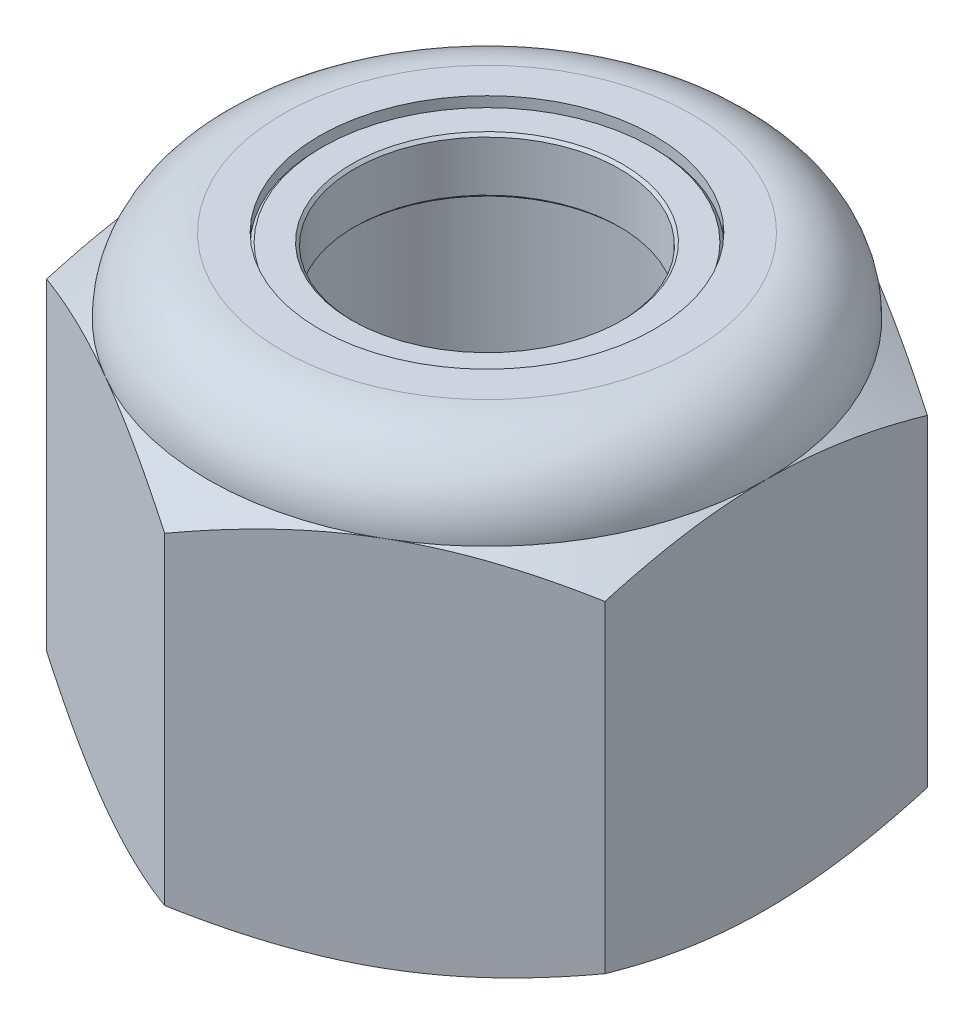
SolidWorks part; units mm, degrees
ref_plane "Front" through (0, 0, 0) normal (0, 0, 1) x (1, 0, 0)
ref_plane "Top" through (0, 0, 0) normal (0, 1, 0) x (1, 0, 0)
ref_plane "Right" through (0, 0, 0) normal (1, 0, 0) x (0, 0, -1)
sketch "Sketch1" plane through (0, 0, 0) normal (0, 1, 0) x (1, 0, 0)
  line L1 (0, 5.7735) -> (-5, 2.8868)
  line L2 (-5, 2.8868) -> (-5, -2.8868)
  line L3 (-5, -2.8868) -> (0, -5.7735)
  line L4 (0, -5.7735) -> (5, -2.8868)
  line L5 (5, -2.8868) -> (5, 2.8868)
  line L6 (5, 2.8868) -> (0, 5.7735)
  circle A0 centre (0, 0) radius 5 construction
  circle A1 centre (0, 0) radius 3
  dimension "Thread Dia" = 6
  dimension "Hex Flats" = 10
extrude "Extrude1" add sketch "Sketch1" along normal blind 8
sketch "Sketch2" plane through (0, 0, 0) normal (1, 0, 0) x (0, 0, -1)
  line L0 (5.7735, 8) -> (5.7735, 0) construction
  line L1 (5.7735, 8) -> (5.7735, 6.2201)
  line L2 (5.7735, 0.4466) -> (5, 0)
  line L3 (5, 0) -> (5.7735, 0)
  line L4 (5, 0) -> (-5, 0) construction
  line L5 (5.7735, 6.2201) -> (5, 6.6667)
  line L6 (2.8868, 8) -> (5.7735, 8) construction
  line L7 (5, 0) -> (5, 6.6667) construction
  line L8 (3.6667, 8) -> (5.7735, 8)
  line L9 (5.7735, 0.4466) -> (5.7735, 0)
  line L10 (0, 0) -> (0, 8) construction
  line L11 (-2.8868, 8) -> (2.8868, 8) construction
  arc A0 (5, 6.6667) -> (3.6667, 8) centre (3.6667, 6.6667) ccw
  dimension "D1" = 30
  dimension "D2" = 30
  dimension "D3" = 1.3333
revolve "Cut-Revolve1" cut sketch "Sketch2" angle 360 about L10
sketch "Sketch4" plane through (0, 0, 0) normal (0, -1, 0) x (1, 0, 0)
  circle A0 centre (0, 0) radius 3 construction
  circle A2 centre (0, 0) radius 3
curve "Helix/Spiral1" pitch 1 height 9 turns 9 parameters "Pitch"=1
sketch "Sketch3" plane through (0, 8, 0) normal (0, 1, 0) x (1, 0, 0)
  circle A0 centre (0, 0) radius 3 construction
  circle A1 centre (0, 0) radius 3
extrude "Extrude-Thin1" add sketch "Sketch3" against normal blind 1 from offset 0.15 separate body thin offset against normal yes thin type one direction reverse wall 0.625
chamfer "Chamfer1" distance 0.05 angle 45 4 edges at (0, 7.85, 3) (2.375, 7.85, 0) (0, 6.85, 3) (2.375, 6.85, 0)
sketch "Sketch5" [suppressed] plane through (0, 0, 0) normal (1, 0, 0) x (0, 0, -1)
  line L0 (3, -0.875) -> (3, 0)
  line L1 (3, -0.875) -> (2.3505, -0.5)
  line L2 (2.3505, -0.5) -> (2.3505, -0.375)
  line L3 (2.3505, -0.375) -> (3, 0)
  line L5 (3, -0.4375) -> (2.3505, -0.4375) construction
  line L6 (2.6752, -0.6875) -> (2.6752, -0.1875) construction
  dimension "D1" = 0.125
  dimension "D2" = 0.5
  dimension "D3" = 60
  dimension "D4" = 0.6495
sweep "Sweep1" [suppressed] add profiles "Sketch5" path "Helix/Spiral1"
sketch "Sketch6" [suppressed] plane through (0, 0, 0) normal (0, -1, 0) x (1, 0, 0)
  circle A1 centre (0, 0) radius 3
  circle A2 centre (0, 0) radius 3
  dimension "D1" = 0
extrude "Cut-Extrude1" [suppressed] cut sketch "Sketch6" against normal through all draft 45 and the other way through all
sketch "Sketch7" [suppressed] plane through (0, 8, 0) normal (0, 1, 0) x (1, 0, 0)
  circle A1 centre (0, 0) radius 3
  circle A2 centre (0, 0) radius 3
  dimension "D1" = 0
extrude "Cut-Extrude2" [suppressed] cut sketch "Sketch7" along normal through all and the other way through all draft 45 from offset 1 offset against normal yes
combine bodies "Combine1" [suppressed] operation type add bodies to combine 138 135
ref_plane "Contact Plane 1" through (0, 0, 0) normal (0, -1, 0) x (-1, 0, 0)
ref_axis "Center Axis 1" [suppressed] through (0, 8.7051, 0) along (0, -1, 0)
equation "\"D3@Helix/Spiral1\"=\"Pitch@Helix/Spiral1\"+\"Height@Extrude1\""
equation "\"D1@Sketch5\"=\"Pitch@Helix/Spiral1\"*.125"
equation "\"D2@Sketch5\"=\"Pitch@Helix/Spiral1\"*.50"
equation "\"D3@Sketch2\"=\"Height@Extrude1\"/6"
equation "\"D5@Extrude-Thin1\"=\"Pitch@Helix/Spiral1\"*.625"
